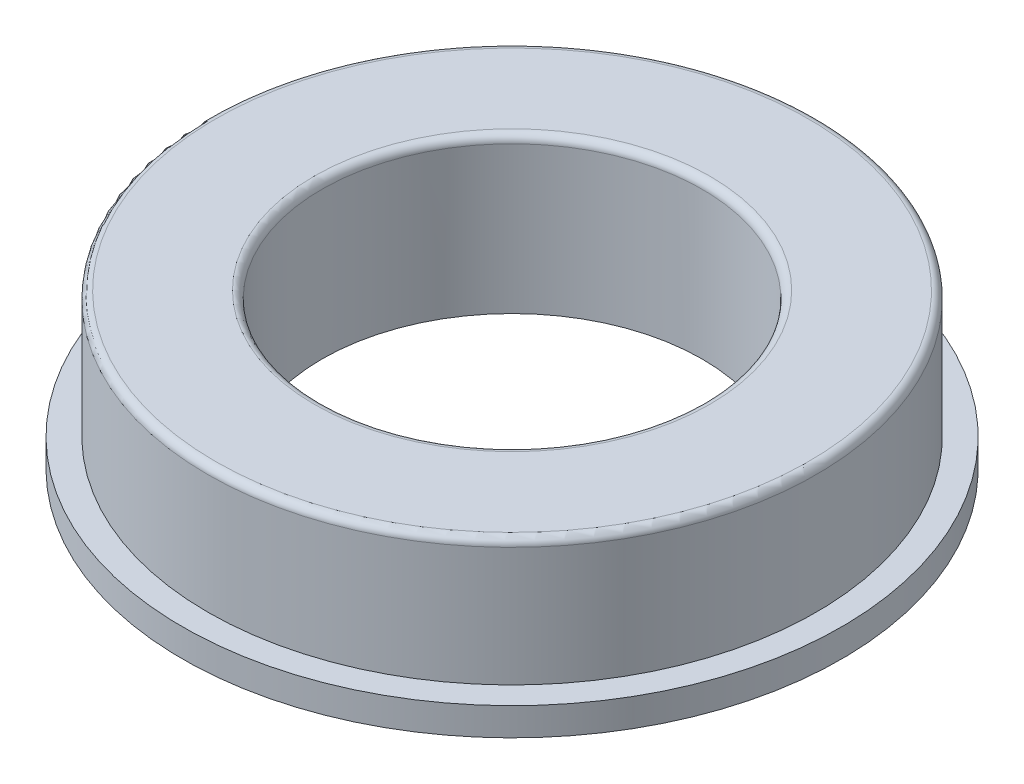
SolidWorks part; units mm, degrees
ref_plane "前视基准面" through (0, 0, 0) normal (0, 0, 1) x (1, 0, 0)
ref_plane "上视基准面" through (0, 0, 0) normal (0, 1, 0) x (1, 0, 0)
ref_plane "右视基准面" through (0, 0, 0) normal (1, 0, 0) x (0, 0, -1)
ref_plane "基准面1" through (0, 0, 0) normal (0, 0, -1) x (-1, 0, 0)
sketch "草图1" plane through (0, 0, 0) normal (0, 0, -1) x (-1, 0, 0)
  line L0 (-11.7, 0) -> (-7.8, 0)
  line L1 (-7.5, 0.3) -> (-7.5, 4.7)
  line L2 (-7.8, 5) -> (-11.7, 5)
  line L3 (-12, 4.7) -> (-12, 0.3)
  line L4 (0, -0.0013) -> (0, 5.0013) construction
  line L5 (-11.7, 0) -> (-12, 0)
  line L6 (-12, 0) -> (-12, 0.3)
  line L7 (-7.5, 0.3) -> (-7.5, 0)
  line L8 (-7.5, 0) -> (-7.8, 0)
  arc A2 (-7.5, 4.7) -> (-7.8, 5) centre (-7.8, 4.7) ccw
  arc A3 (-11.7, 5) -> (-12, 4.7) centre (-11.7, 4.7) ccw
revolve "旋转1" add sketch "草图1" angle 360 about L4 reverse direction yes
sketch "草图2" plane through (0, 0, 0) normal (0, -1, 0) x (1, 0, 0)
  circle A0 centre (0, 0) radius 13
  dimension "D1" = 26
extrude "凸台-拉伸1" add sketch "草图2" along normal blind 1.1
sketch "草图3" plane through (0, 0, 0) normal (0, 1, 0) x (1, 0, 0)
  circle A0 centre (0, 0) radius 7.5
extrude "切除-拉伸1" cut sketch "草图3" against normal up to next
